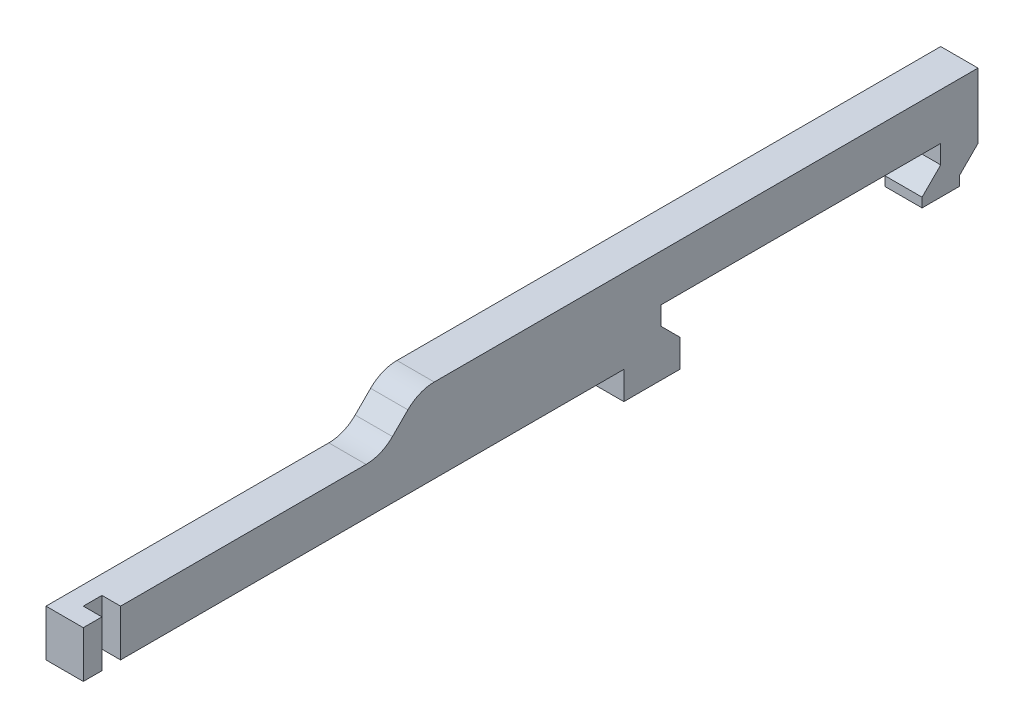
SolidWorks part; units mm, degrees
ref_plane "Спереди" through (0, 0, 0) normal (0, 0, 1) x (1, 0, 0)
ref_plane "Сверху" through (0, 0, 0) normal (0, 1, 0) x (1, 0, 0)
ref_plane "Справа" through (0, 0, 0) normal (1, 0, 0) x (0, 0, -1)
sketch "Эскиз1" plane through (0, 0, 0) normal (1, 0, 0) x (0, 0, -1)
  line L0 (16, 2.5) -> (18, 4.5)
  line L1 (0, 0) -> (16, 0)
  line L2 (0, 0) -> (0, 2.5)
  line L3 (0, 2.5) -> (16, 2.5)
  line L4 (16, 0) -> (16, 2.5)
  line L5 (18, 4.5) -> (18, 2.5) construction
  line L6 (18, 2.5) -> (16, 2.5) construction
  line L7 (18, 4.5) -> (29, 4.5)
  line L8 (16, 0) -> (29, 0)
  line L9 (29, 0) -> (29, -1.5)
  line L10 (29, -1.5) -> (32, -1.5)
  line L11 (32, -1.5) -> (32, 0)
  line L12 (32, 0) -> (31, 1)
  line L13 (31, 1) -> (31, 2)
  line L14 (31, 2) -> (46, 2)
  line L15 (32, 0) -> (31, 0) construction
  line L16 (31, 0) -> (31, 1) construction
  line L17 (38.5, 2) -> (38.5, 1) construction
  line L18 (45, 0) -> (46, 1)
  line L19 (46, 1) -> (46, 2)
  line L20 (45, 0) -> (45, -0.5)
  line L21 (45, -0.5) -> (47, -0.5)
  line L22 (47, -0.5) -> (47, 0)
  line L23 (47, 0) -> (48, 1)
  line L24 (48, 1) -> (48, 4.5)
  line L25 (48, 4.5) -> (29, 4.5)
  dimension "D1" = 2.5
  dimension "D2" = 16
  dimension "D3" = 2
  dimension "D4" = 2
  dimension "D5" = 11
  dimension "D6" = 13
  dimension "D7" = 1.5
  dimension "D8" = 3
  dimension "D9" = 1.5
  dimension "D10" = 1
  dimension "D11" = 1
  dimension "D12" = 1
  dimension "D13" = 15
  dimension "D14" = 0.5
  dimension "D15" = 2
extrude "Бобышка-Вытянуть1" add sketch "Эскиз1" along normal blind 2 contours L24 L25 L7 L0 L4 L8 L9 L10 L11 L12 L13 L14 L19 L18 L20 L21 L22 L23 | L1 L4 L3 L2 region at (0, 1.25, -8) region at (0, 2.3972, -30.6575)
fillet "Скругление1" radius 2 2 edges at (1, 4.5, -18) (1, 2.5, -16)
sketch "Эскиз2" plane through (0, 2.5, 0) normal (0, 1, 0) x (1, 0, 0)
  line L0 (2, 0) -> (2, 1) construction
  line L1 (2, 0) -> (2, 15.1716) construction
  line L3 (2, 1) -> (1, 1)
  line L4 (2, 1) -> (2, 2)
  line L5 (2, 2) -> (1, 2)
  line L6 (1, 1) -> (1, 2)
  dimension "D1" = 1
  dimension "D2" = 1
  dimension "D3" = 1
extrude "Вырез-Вытянуть1" cut sketch "Эскиз2" against normal through all
